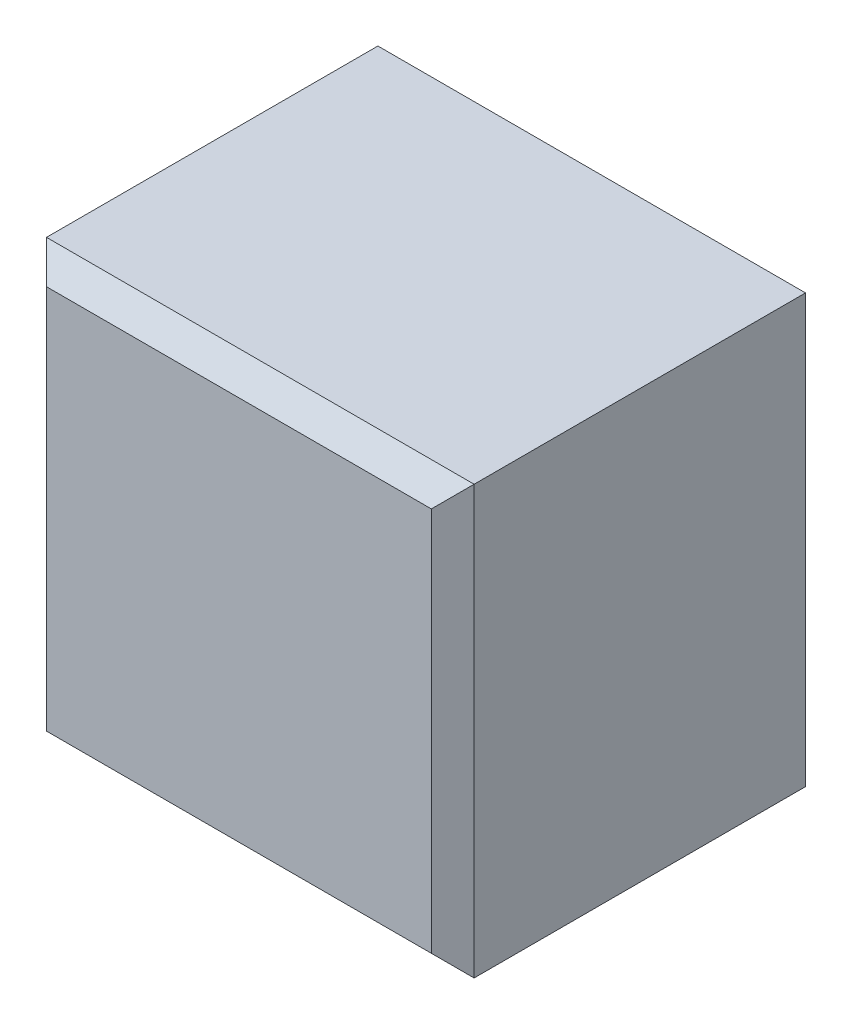
SolidWorks part; units mm, degrees
ref_plane "Front Plane" through (0, 0, 0) normal (0, 0, 1) x (1, 0, 0)
ref_plane "Top Plane" through (0, 0, 0) normal (0, 1, 0) x (1, 0, 0)
ref_plane "Right Plane" through (0, 0, 0) normal (1, 0, 0) x (0, 0, -1)
sketch "Sketch1" plane through (0, 0, 0) normal (0, 1, 0) x (1, 0, 0)
  line L0 (0, 15.4105) -> (0, -23.6813) construction
  line L1 (-10, 8.75) -> (10, 8.75)
  line L2 (-10, 8.75) -> (-10, -8.75)
  line L3 (-10, -8.75) -> (10, -8.75)
  line L4 (10, 8.75) -> (10, -8.75)
  line L5 (-21.5466, 0) -> (26.5733, 0) construction
  dimension "D1" = 17.5
  dimension "D2" = 20
extrude "Boss-Extrude1" add sketch "Sketch1" along normal blind 10 and the other way blind 10
chamfer "Chamfer2" distance 1 angle 45 8 edges at (-10, 0, 8.75) (0, 10, 8.75) (10, 0, 8.75) (0, -10, 8.75) (10, 0, -8.75) (0, 10, -8.75) (-10, 0, -8.75) (0, -10, -8.75)
